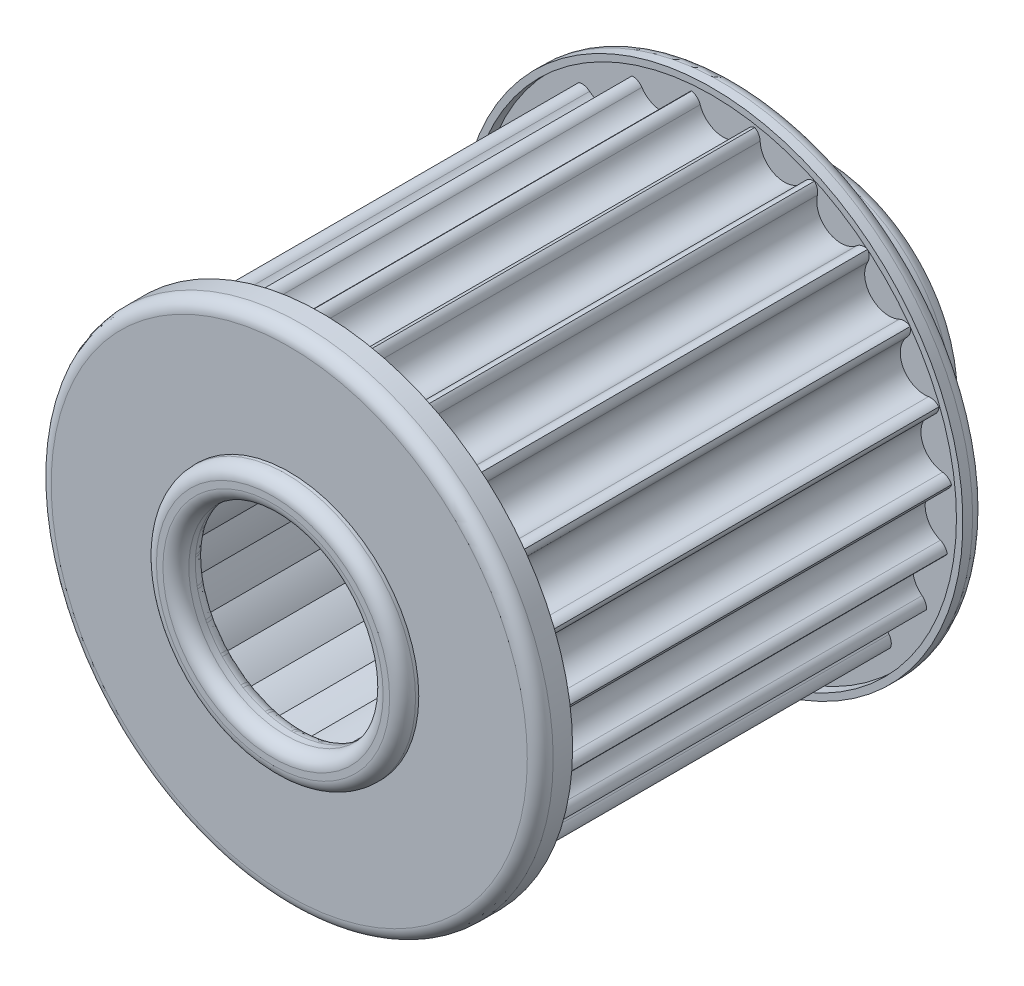
SolidWorks part; units mm, degrees
ref_plane "Front Plane" through (0, 0, 0) normal (0, 0, 1) x (1, 0, 0)
ref_plane "Top Plane" through (0, 0, 0) normal (0, 1, 0) x (1, 0, 0)
ref_plane "Right Plane" through (0, 0, 0) normal (1, 0, 0) x (0, 0, -1)
sketch "Sketch2" plane through (0, 0, 0) normal (0, 1, 0) x (1, 0, 0)
  line L0 (37.5, 21.1002) -> (37.5, 17.6002)
  line L1 (37.5, 17.6002) -> (39.5, 17.6002)
  line L2 (39.5, 17.6002) -> (39.5, 21.1002)
  line L10 (0, 52.6002) -> (0, 0.224) construction
  line L11 (43, 52.6002) -> (37.5, 52.6002)
  line L12 (75.5, 21.1002) -> (75.5, 17.6002)
  line L13 (75.5, 17.6002) -> (77.5, 17.6002)
  line L14 (77.5, 17.6002) -> (77.5, 24.6002)
  line L15 (77.5, 24.6002) -> (50, 24.6002)
  line L16 (50, 24.6002) -> (43, 31.6002)
  line L17 (43, 31.6002) -> (43, 52.6002)
  line L18 (37.5, 52.6002) -> (37.5, 21.1002)
  line L19 (39.5, 21.1002) -> (75.5, 21.1002)
  dimension "D1" = 37.5
  dimension "D2" = 2
revolve "Revolve2" add sketch "Sketch2" angle 360 about L10
sketch "Sketch3" plane through (0, 0, -21.1002) normal (0, 0, 1) x (1, 0, 0)
  circle A0 centre (0, 0) radius 72.5
  dimension "D1" = 145
extrude "Boss-Extrude1" add sketch "Sketch3" along normal blind 128
sketch "Sketch4" plane through (0, 0, 106.8998) normal (0, 0, 1) x (1, 0, 0)
  line L0 (7.5, 70) -> (10, 70)
  line L1 (-10, 70) -> (-7.5, 70)
  line L2 (-10, 70) -> (-10, 74.8348)
  line L4 (10, 70) -> (10, 74.8348)
  arc A0 (-7.5, 70) -> (7.5, 70) centre (0, 70) ccw
  circle A1 centre (0, 0) radius 75.5 construction
  arc A2 (10, 74.8348) -> (-10, 74.8348) centre (0, 0) ccw
  dimension "D1" = 15
  dimension "D2" = 70
  dimension "D3" = 10
  dimension "D4" = 10
extrude "Cut-Extrude1" cut sketch "Sketch4" against normal up to surface (128 mm away) up to face at (-72.5, 0, -21.1002)
fillet "Fillet1" radius 3.5 2 edges at (7.5, 70, 42.8998) (-7.5, 70, 42.8998)
pattern_circular "CirPattern1" count 23 over 360 about axis through (0, 0, 106.8998) along (0, 0, 1) of "Cut-Extrude1", "Fillet1"
sketch "Sketch5" plane through (0, 0, 106.8998) normal (0, 0, 1) x (1, 0, 0)
  arc A0 (-34.5026, 42.4094) -> (-21.7812, 50.1454) centre (-36.3709, 59.8094) ccw
  arc A1 (-21.7812, 50.1454) -> (-21.7812, 50.1454) centre (-21.7812, 50.1454) ccw
  arc A2 (-21.7812, 50.1454) -> (-21.7812, 50.1454) centre (-21.7812, 50.1454) ccw
  arc A3 (-21.7812, 50.1454) -> (-7.4444, 54.1624) centre (-18.8858, 67.4042) ccw
  arc A4 (-7.4444, 54.1624) -> (-7.4444, 54.1624) centre (-7.4444, 54.1624) ccw
  arc A5 (-7.4444, 54.1624) -> (-7.4444, 54.1624) centre (-7.4444, 54.1624) ccw
  arc A6 (-7.4444, 54.1624) -> (7.4444, 54.1624) centre (0, 70) ccw
  arc A7 (7.4444, 54.1624) -> (7.4444, 54.1624) centre (7.4444, 54.1624) ccw
  arc A8 (7.4444, 54.1624) -> (7.4444, 54.1624) centre (7.4444, 54.1624) ccw
  arc A9 (7.4444, 54.1624) -> (21.7812, 50.1454) centre (18.8858, 67.4042) ccw
  arc A10 (21.7812, 50.1454) -> (21.7812, 50.1454) centre (21.7812, 50.1454) ccw
  arc A11 (21.7812, 50.1454) -> (21.7812, 50.1454) centre (21.7812, 50.1454) ccw
  arc A12 (21.7812, 50.1454) -> (34.5026, 42.4094) centre (36.3709, 59.8094) ccw
  arc A13 (34.5026, 42.4094) -> (34.5026, 42.4094) centre (34.5026, 42.4094) ccw
  arc A14 (34.5026, 42.4094) -> (34.5026, 42.4094) centre (34.5026, 42.4094) ccw
  arc A15 (34.5026, 42.4094) -> (44.665, 31.528) centre (51.1585, 47.7787) ccw
  arc A16 (44.665, 31.528) -> (44.665, 31.528) centre (44.665, 31.528) ccw
  arc A17 (44.665, 31.528) -> (44.665, 31.528) centre (44.665, 31.528) ccw
  arc A18 (44.665, 31.528) -> (51.5149, 18.3084) centre (62.152, 32.2046) ccw
  arc A19 (51.5149, 18.3084) -> (51.5149, 18.3084) centre (51.5149, 18.3084) ccw
  arc A20 (51.5149, 18.3084) -> (51.5149, 18.3084) centre (51.5149, 18.3084) ccw
  arc A21 (51.5149, 18.3084) -> (54.5441, 3.7309) centre (68.5359, 14.2419) ccw
  arc A22 (54.5441, 3.7309) -> (54.5441, 3.7309) centre (54.5441, 3.7309) ccw
  arc A23 (54.5441, 3.7309) -> (54.5441, 3.7309) centre (54.5441, 3.7309) ccw
  arc A24 (54.5441, 3.7309) -> (53.5281, -11.1233) centre (69.8368, -4.777) ccw
  arc A25 (53.5281, -11.1233) -> (53.5281, -11.1233) centre (53.5281, -11.1233) ccw
  arc A26 (53.5281, -11.1233) -> (53.5281, -11.1233) centre (53.5281, -11.1233) ccw
  arc A27 (53.5281, -11.1233) -> (48.5421, -25.1525) centre (65.9583, -23.4416) ccw
  arc A28 (48.5421, -25.1525) -> (48.5421, -25.1525) centre (48.5421, -25.1525) ccw
  arc A29 (48.5421, -25.1525) -> (48.5421, -25.1525) centre (48.5421, -25.1525) ccw
  arc A30 (48.5421, -25.1525) -> (39.956, -37.3163) centre (57.1879, -40.3676) ccw
  arc A31 (39.956, -37.3163) -> (39.956, -37.3163) centre (39.956, -37.3163) ccw
  arc A32 (39.956, -37.3163) -> (39.956, -37.3163) centre (39.956, -37.3163) ccw
  arc A33 (39.956, -37.3163) -> (28.4065, -46.7125) centre (44.1762, -54.2998) ccw
  arc A34 (28.4065, -46.7125) -> (28.4065, -46.7125) centre (28.4065, -46.7125) ccw
  arc A35 (28.4065, -46.7125) -> (28.4065, -46.7125) centre (28.4065, -46.7125) ccw
  arc A36 (28.4065, -46.7125) -> (14.7502, -52.6442) centre (27.8881, -64.2048) ccw
  arc A37 (14.7502, -52.6442) -> (14.7502, -52.6442) centre (14.7502, -52.6442) ccw
  arc A38 (14.7502, -52.6442) -> (14.7502, -52.6442) centre (14.7502, -52.6442) ccw
  arc A39 (14.7502, -52.6442) -> (0, -54.6716) centre (9.5317, -69.348) ccw
  arc A40 (0, -54.6716) -> (0, -54.6716) centre (0, -54.6716) ccw
  arc A41 (0, -54.6716) -> (0, -54.6716) centre (0, -54.6716) ccw
  arc A42 (0, -54.6716) -> (-14.7502, -52.6442) centre (-9.5317, -69.348) ccw
  arc A43 (-14.7502, -52.6442) -> (-14.7502, -52.6442) centre (-14.7502, -52.6442) ccw
  arc A44 (-14.7502, -52.6442) -> (-14.7502, -52.6442) centre (-14.7502, -52.6442) ccw
  arc A45 (-14.7502, -52.6442) -> (-28.4065, -46.7125) centre (-27.8881, -64.2048) ccw
  arc A46 (-28.4065, -46.7125) -> (-28.4065, -46.7125) centre (-28.4065, -46.7125) ccw
  arc A47 (-28.4065, -46.7125) -> (-28.4065, -46.7125) centre (-28.4065, -46.7125) ccw
  arc A48 (-28.4065, -46.7125) -> (-39.956, -37.3163) centre (-44.1762, -54.2998) ccw
  arc A49 (-39.956, -37.3163) -> (-39.956, -37.3163) centre (-39.956, -37.3163) ccw
  arc A50 (-39.956, -37.3163) -> (-39.956, -37.3163) centre (-39.956, -37.3163) ccw
  arc A51 (-39.956, -37.3163) -> (-48.5421, -25.1525) centre (-57.1879, -40.3676) ccw
  arc A52 (-48.5421, -25.1525) -> (-48.5421, -25.1525) centre (-48.5421, -25.1525) ccw
  arc A53 (-48.5421, -25.1525) -> (-48.5421, -25.1525) centre (-48.5421, -25.1525) ccw
  arc A54 (-48.5421, -25.1525) -> (-53.5281, -11.1233) centre (-65.9583, -23.4416) ccw
  arc A55 (-53.5281, -11.1233) -> (-53.5281, -11.1233) centre (-53.5281, -11.1233) ccw
  arc A56 (-53.5281, -11.1233) -> (-53.5281, -11.1233) centre (-53.5281, -11.1233) ccw
  arc A57 (-53.5281, -11.1233) -> (-54.5441, 3.7309) centre (-69.8368, -4.777) ccw
  arc A58 (-54.5441, 3.7309) -> (-54.5441, 3.7309) centre (-54.5441, 3.7309) ccw
  arc A59 (-54.5441, 3.7309) -> (-54.5441, 3.7309) centre (-54.5441, 3.7309) ccw
  arc A60 (-54.5441, 3.7309) -> (-51.5149, 18.3084) centre (-68.5359, 14.2419) ccw
  arc A61 (-51.5149, 18.3084) -> (-51.5149, 18.3084) centre (-51.5149, 18.3084) ccw
  arc A62 (-51.5149, 18.3084) -> (-51.5149, 18.3084) centre (-51.5149, 18.3084) ccw
  arc A63 (-51.5149, 18.3084) -> (-44.665, 31.528) centre (-62.152, 32.2046) ccw
  arc A64 (-44.665, 31.528) -> (-44.665, 31.528) centre (-44.665, 31.528) ccw
  arc A65 (-44.665, 31.528) -> (-44.665, 31.528) centre (-44.665, 31.528) ccw
  arc A66 (-44.665, 31.528) -> (-34.5026, 42.4094) centre (-51.1585, 47.7787) ccw
  arc A67 (-34.5026, 42.4094) -> (-34.5026, 42.4094) centre (-34.5026, 42.4094) ccw
  arc A68 (-34.5026, 42.4094) -> (-34.5026, 42.4094) centre (-34.5026, 42.4094) ccw
  arc A69 (29.0724, 61.5365) -> (28.1503, 64.8084) centre (25.6665, 62.3425) ccw
  arc A70 (28.1503, 64.8084) -> (25.1296, 63.2491) centre (28.0434, 61.3101) ccw
  arc A71 (11.3908, 67.1289) -> (25.1296, 63.2491) centre (18.8858, 67.4042) ccw
  arc A72 (11.3908, 67.1289) -> (9.7597, 69.9612) centre (7.8932, 67.0005) ccw
  arc A73 (9.7597, 69.9612) -> (7.1165, 67.6324) centre (10.4375, 66.5275) ccw
  arc A74 (-7.1165, 67.6324) -> (7.1165, 67.6324) centre (0, 70) ccw
  arc A75 (-7.1165, 67.6324) -> (-9.7597, 69.9612) centre (-10.4375, 66.5275) ccw
  arc A76 (-9.7597, 69.9612) -> (-11.3908, 67.1289) centre (-7.8932, 67.0005) ccw
  arc A77 (-25.1296, 63.2491) -> (-11.3908, 67.1289) centre (-18.8858, 67.4042) ccw
  arc A78 (-25.1296, 63.2491) -> (-28.1503, 64.8084) centre (-28.0434, 61.3101) ccw
  arc A79 (-28.1503, 64.8084) -> (-29.0724, 61.5365) centre (-25.6665, 62.3425) ccw
  arc A80 (-41.2621, 54.1238) -> (-29.0724, 61.5365) centre (-36.3709, 59.8094) ccw
  arc A81 (-41.2621, 54.1238) -> (-44.5915, 54.8103) centre (-43.5447, 51.4705) ccw
  arc A82 (-44.5915, 54.8103) -> (-44.5967, 51.4109) centre (-41.5345, 53.1059) ccw
  arc A83 (-54.3344, 40.9843) -> (-44.5967, 51.4109) centre (-51.1585, 47.7787) ccw
  arc A84 (-54.3344, 40.9843) -> (-57.7256, 40.7471) centre (-55.8165, 37.8136) ccw
  arc A85 (-57.7256, 40.7471) -> (-56.8134, 37.4724) centre (-54.3221, 39.9307) ccw
  arc A86 (-63.377, 24.8053) -> (-56.8134, 37.4724) centre (-62.152, 32.2046) ccw
  arc A87 (-63.377, 24.8053) -> (-66.5784, 23.662) centre (-63.9487, 21.3523) ccw
  arc A88 (-66.5784, 23.662) -> (-64.8166, 20.7547) centre (-63.0809, 23.794) ccw
  arc A89 (-67.7192, 6.7865) -> (-64.8166, 20.7547) centre (-68.5359, 14.2419) ccw
  arc A90 (-67.7192, 6.7865) -> (-70.4934, 4.8219) centre (-67.3381, 3.3073) ccw
  arc A91 (-70.4934, 4.8219) -> (-68.0125, 2.4978) centre (-67.1612, 5.8927) ccw
  arc A92 (-67.039, -11.7356) -> (-68.0125, 2.4978) centre (-69.8368, -4.777) ccw
  arc A93 (-67.039, -11.7356) -> (-69.1802, -14.3758) centre (-65.7333, -14.9829) ccw
  arc A94 (-69.1802, -14.3758) -> (-66.1643, -15.9444) centre (-66.2605, -12.4457) ccw
  arc A95 (-61.3868, -29.3873) -> (-66.1643, -15.9444) centre (-65.9583, -23.4416) ccw
  arc A96 (-61.3868, -29.3873) -> (-62.7363, -32.5073) centre (-59.2534, -32.1619) ccw
  arc A97 (-62.7363, -32.5073) -> (-59.409, -33.2041) centre (-60.4456, -29.8611) ccw
  arc A98 (-51.1818, -44.8595) -> (-59.409, -33.2041) centre (-57.1879, -40.3676) ccw
  arc A99 (-51.1818, -44.8595) -> (-51.6395, -48.2279) centre (-48.3789, -46.9556) ccw
  arc A100 (-51.6395, -48.2279) -> (-48.2476, -48.0011) centre (-50.1477, -45.0618) ccw
  arc A101 (-37.1809, -57.0046) -> (-48.2476, -48.0011) centre (-44.1762, -54.2998) ccw
  arc A102 (-37.1809, -57.0046) -> (-36.7128, -60.3717) centre (-33.9164, -58.2669) ccw
  arc A103 (-36.7128, -60.3717) -> (-33.5079, -59.2382) centre (-36.1305, -56.9204) ccw
  arc A104 (-20.4224, -64.922) -> (-33.5079, -59.2382) centre (-27.8881, -64.2048) ccw
  arc A105 (-20.4224, -64.922) -> (-19.0633, -68.0379) centre (-16.9385, -65.2567) ccw
  arc A106 (-19.0633, -68.0379) -> (-16.2831, -66.0818) centre (-19.4338, -64.5576) ccw
  arc A107 (-2.1494, -68.0244) -> (-16.2831, -66.0818) centre (-9.5317, -69.348) ccw
  arc A108 (-2.1494, -68.0244) -> (0, -70.6581) centre (1.2957, -67.4068) ccw
  arc A109 (0, -70.6581) -> (2.1494, -68.0244) centre (-1.2957, -67.4068) ccw
  arc A110 (16.2831, -66.0818) -> (2.1494, -68.0244) centre (9.5317, -69.348) ccw
  arc A111 (16.2831, -66.0818) -> (19.0633, -68.0379) centre (19.4338, -64.5576) ccw
  arc A112 (19.0633, -68.0379) -> (20.4224, -64.922) centre (16.9385, -65.2567) ccw
  arc A113 (33.5079, -59.2382) -> (20.4224, -64.922) centre (27.8881, -64.2048) ccw
  arc A114 (33.5079, -59.2382) -> (36.7128, -60.3717) centre (36.1305, -56.9204) ccw
  arc A115 (36.7128, -60.3717) -> (37.1809, -57.0046) centre (33.9164, -58.2669) ccw
  arc A116 (48.2476, -48.0011) -> (37.1809, -57.0046) centre (44.1762, -54.2998) ccw
  arc A117 (48.2476, -48.0011) -> (51.6395, -48.2279) centre (50.1477, -45.0618) ccw
  arc A118 (51.6395, -48.2279) -> (51.1818, -44.8595) centre (48.3789, -46.9556) ccw
  arc A119 (59.409, -33.2041) -> (51.1818, -44.8595) centre (57.1879, -40.3676) ccw
  arc A120 (59.409, -33.2041) -> (62.7363, -32.5073) centre (60.4456, -29.8611) ccw
  arc A121 (62.7363, -32.5073) -> (61.3868, -29.3873) centre (59.2534, -32.1619) ccw
  arc A122 (66.1643, -15.9444) -> (61.3868, -29.3873) centre (65.9583, -23.4416) ccw
  arc A123 (66.1643, -15.9444) -> (69.1802, -14.3758) centre (66.2605, -12.4457) ccw
  arc A124 (69.1802, -14.3758) -> (67.039, -11.7356) centre (65.7333, -14.9829) ccw
  arc A125 (68.0125, 2.4978) -> (67.039, -11.7356) centre (69.8368, -4.777) ccw
  arc A126 (68.0125, 2.4978) -> (70.4934, 4.8219) centre (67.1612, 5.8927) ccw
  arc A127 (70.4934, 4.8219) -> (67.7192, 6.7865) centre (67.3381, 3.3073) ccw
  arc A128 (64.8166, 20.7547) -> (67.7192, 6.7865) centre (68.5359, 14.2419) ccw
  arc A129 (64.8166, 20.7547) -> (66.5784, 23.662) centre (63.0809, 23.794) ccw
  arc A130 (66.5784, 23.662) -> (63.377, 24.8053) centre (63.9487, 21.3523) ccw
  arc A131 (56.8134, 37.4724) -> (63.377, 24.8053) centre (62.152, 32.2046) ccw
  arc A132 (56.8134, 37.4724) -> (57.7256, 40.7471) centre (54.3221, 39.9307) ccw
  arc A133 (57.7256, 40.7471) -> (54.3344, 40.9843) centre (55.8165, 37.8136) ccw
  arc A134 (44.5967, 51.4109) -> (54.3344, 40.9843) centre (51.1585, 47.7787) ccw
  arc A135 (44.5967, 51.4109) -> (44.5915, 54.8103) centre (41.5345, 53.1059) ccw
  arc A136 (44.5915, 54.8103) -> (41.2621, 54.1238) centre (43.5447, 51.4705) ccw
  arc A137 (29.0724, 61.5365) -> (41.2621, 54.1238) centre (36.3709, 59.8094) ccw
  arc A138 (29.0724, 61.5365) -> (28.1503, 64.8084) centre (25.6665, 62.3425) ccw
  arc A139 (28.1503, 64.8084) -> (25.1296, 63.2491) centre (28.0434, 61.3101) ccw
  arc A141 (11.3908, 67.1289) -> (9.7597, 69.9612) centre (7.8932, 67.0005) ccw
  arc A142 (9.7597, 69.9612) -> (7.1165, 67.6324) centre (10.4375, 66.5275) ccw
  arc A144 (-7.1165, 67.6324) -> (-9.7597, 69.9612) centre (-10.4375, 66.5275) ccw
  arc A150 (-41.2621, 54.1238) -> (-44.5915, 54.8103) centre (-43.5447, 51.4705) ccw
  arc A151 (-44.5915, 54.8103) -> (-44.5967, 51.4109) centre (-41.5345, 53.1059) ccw
  arc A153 (-54.3344, 40.9843) -> (-57.7256, 40.7471) centre (-55.8165, 37.8136) ccw
  arc A154 (-57.7256, 40.7471) -> (-56.8134, 37.4724) centre (-54.3221, 39.9307) ccw
  arc A155 (-63.377, 24.8053) -> (-56.8134, 37.4724) centre (-62.152, 32.2046) ccw
  arc A156 (-63.377, 24.8053) -> (-66.5784, 23.662) centre (-63.9487, 21.3523) ccw
  arc A157 (-66.5784, 23.662) -> (-64.8166, 20.7547) centre (-63.0809, 23.794) ccw
  arc A162 (-67.039, -11.7356) -> (-69.1802, -14.3758) centre (-65.7333, -14.9829) ccw
  arc A163 (-69.1802, -14.3758) -> (-66.1643, -15.9444) centre (-66.2605, -12.4457) ccw
  arc A165 (-61.3868, -29.3873) -> (-62.7363, -32.5073) centre (-59.2534, -32.1619) ccw
  arc A166 (-62.7363, -32.5073) -> (-59.409, -33.2041) centre (-60.4456, -29.8611) ccw
  arc A168 (-51.1818, -44.8595) -> (-51.6395, -48.2279) centre (-48.3789, -46.9556) ccw
  arc A169 (-51.6395, -48.2279) -> (-48.2476, -48.0011) centre (-50.1477, -45.0618) ccw
  arc A171 (-37.1809, -57.0046) -> (-36.7128, -60.3717) centre (-33.9164, -58.2669) ccw
  arc A172 (-36.7128, -60.3717) -> (-33.5079, -59.2382) centre (-36.1305, -56.9204) ccw
  arc A174 (-20.4224, -64.922) -> (-19.0633, -68.0379) centre (-16.9385, -65.2567) ccw
  arc A175 (-19.0633, -68.0379) -> (-16.2831, -66.0818) centre (-19.4338, -64.5576) ccw
  arc A177 (-2.1494, -68.0244) -> (0, -70.6581) centre (1.2957, -67.4068) ccw
  arc A178 (0, -70.6581) -> (2.1494, -68.0244) centre (-1.2957, -67.4068) ccw
  arc A180 (16.2831, -66.0818) -> (19.0633, -68.0379) centre (19.4338, -64.5576) ccw
  arc A181 (19.0633, -68.0379) -> (20.4224, -64.922) centre (16.9385, -65.2567) ccw
  arc A183 (33.5079, -59.2382) -> (36.7128, -60.3717) centre (36.1305, -56.9204) ccw
  arc A184 (36.7128, -60.3717) -> (37.1809, -57.0046) centre (33.9164, -58.2669) ccw
  arc A186 (48.2476, -48.0011) -> (51.6395, -48.2279) centre (50.1477, -45.0618) ccw
  arc A187 (51.6395, -48.2279) -> (51.1818, -44.8595) centre (48.3789, -46.9556) ccw
  arc A188 (59.409, -33.2041) -> (51.1818, -44.8595) centre (57.1879, -40.3676) ccw
  arc A189 (59.409, -33.2041) -> (62.7363, -32.5073) centre (60.4456, -29.8611) ccw
  arc A190 (62.7363, -32.5073) -> (61.3868, -29.3873) centre (59.2534, -32.1619) ccw
  arc A192 (66.1643, -15.9444) -> (69.1802, -14.3758) centre (66.2605, -12.4457) ccw
  arc A193 (69.1802, -14.3758) -> (67.039, -11.7356) centre (65.7333, -14.9829) ccw
  arc A197 (64.8166, 20.7547) -> (67.7192, 6.7865) centre (68.5359, 14.2419) ccw
  arc A199 (66.5784, 23.662) -> (63.377, 24.8053) centre (63.9487, 21.3523) ccw
  arc A201 (56.8134, 37.4724) -> (57.7256, 40.7471) centre (54.3221, 39.9307) ccw
  arc A202 (57.7256, 40.7471) -> (54.3344, 40.9843) centre (55.8165, 37.8136) ccw
  arc A204 (44.5967, 51.4109) -> (44.5915, 54.8103) centre (41.5345, 53.1059) ccw
  arc A205 (44.5915, 54.8103) -> (41.2621, 54.1238) centre (43.5447, 51.4705) ccw
  arc A207 (29.0724, 61.5365) -> (41.2621, 54.1238) centre (36.3709, 59.8094) ccw construction
  arc A208 (-7.1165, 67.6324) -> (7.1165, 67.6324) centre (0, 70) ccw construction
  arc A209 (-9.7597, 69.9612) -> (-11.3908, 67.1289) centre (-7.8932, 67.0005) ccw construction
  arc A210 (-25.1296, 63.2491) -> (-28.1503, 64.8084) centre (-28.0434, 61.3101) ccw construction
  arc A211 (-28.1503, 64.8084) -> (-29.0724, 61.5365) centre (-25.6665, 62.3425) ccw construction
  arc A212 (-41.2621, 54.1238) -> (-29.0724, 61.5365) centre (-36.3709, 59.8094) ccw construction
  arc A213 (-25.1296, 63.2491) -> (-11.3908, 67.1289) centre (-18.8858, 67.4042) ccw construction
  arc A214 (-54.3344, 40.9843) -> (-44.5967, 51.4109) centre (-51.1585, 47.7787) ccw construction
  arc A215 (-67.7192, 6.7865) -> (-64.8166, 20.7547) centre (-68.5359, 14.2419) ccw construction
  arc A216 (-67.7192, 6.7865) -> (-70.4934, 4.8219) centre (-67.3381, 3.3073) ccw construction
  arc A217 (-70.4934, 4.8219) -> (-68.0125, 2.4978) centre (-67.1612, 5.8927) ccw construction
  arc A218 (-67.039, -11.7356) -> (-68.0125, 2.4978) centre (-69.8368, -4.777) ccw construction
  arc A219 (-61.3868, -29.3873) -> (-66.1643, -15.9444) centre (-65.9583, -23.4416) ccw construction
  arc A220 (-51.1818, -44.8595) -> (-59.409, -33.2041) centre (-57.1879, -40.3676) ccw construction
  arc A221 (-37.1809, -57.0046) -> (-48.2476, -48.0011) centre (-44.1762, -54.2998) ccw construction
  arc A222 (-20.4224, -64.922) -> (-33.5079, -59.2382) centre (-27.8881, -64.2048) ccw construction
  arc A223 (-2.1494, -68.0244) -> (-16.2831, -66.0818) centre (-9.5317, -69.348) ccw construction
  arc A224 (16.2831, -66.0818) -> (2.1494, -68.0244) centre (9.5317, -69.348) ccw construction
  arc A225 (33.5079, -59.2382) -> (20.4224, -64.922) centre (27.8881, -64.2048) ccw construction
  arc A226 (48.2476, -48.0011) -> (37.1809, -57.0046) centre (44.1762, -54.2998) ccw construction
  arc A227 (66.1643, -15.9444) -> (61.3868, -29.3873) centre (65.9583, -23.4416) ccw construction
  arc A228 (68.0125, 2.4978) -> (67.039, -11.7356) centre (69.8368, -4.777) ccw construction
  arc A229 (68.0125, 2.4978) -> (70.4934, 4.8219) centre (67.1612, 5.8927) ccw construction
  arc A230 (70.4934, 4.8219) -> (67.7192, 6.7865) centre (67.3381, 3.3073) ccw construction
  arc A231 (64.8166, 20.7547) -> (66.5784, 23.662) centre (63.0809, 23.794) ccw construction
  arc A232 (56.8134, 37.4724) -> (63.377, 24.8053) centre (62.152, 32.2046) ccw construction
  arc A233 (44.5967, 51.4109) -> (54.3344, 40.9843) centre (51.1585, 47.7787) ccw construction
  arc A234 (11.3908, 67.1289) -> (25.1296, 63.2491) centre (18.8858, 67.4042) ccw construction
  dimension "D1" = 0
  dimension "D2" = 10
extrude "Cut-Extrude2" cut sketch "Sketch5" against normal blind 128 contours A66 A63 A60 A57 A54 A51 A48 A45 A42 A39 A36 A33 A30 A27 A24 A21 A18 A15 A12 A9 A6 A3 A0 region at (0, 0, 106.8998)
ref_plane "Plane1" through (0, 0, 59.3998) normal (0, 0, -1) x (-1, 0, 0)
sketch "Sketch6" plane through (0, 0, 59.3998) normal (0, 0, -1) x (-1, 0, 0)
  arc A23 (34.5026, 42.4094) -> (44.665, 31.528) centre (51.1585, 47.7787) ccw
  arc A24 (44.665, 31.528) -> (51.5149, 18.3084) centre (62.152, 32.2046) ccw
  arc A25 (51.5149, 18.3084) -> (54.5441, 3.7309) centre (68.5359, 14.2419) ccw
  arc A26 (54.5441, 3.7309) -> (53.5281, -11.1233) centre (69.8368, -4.777) ccw
  arc A27 (53.5281, -11.1233) -> (48.5421, -25.1525) centre (65.9583, -23.4416) ccw
  arc A28 (48.5421, -25.1525) -> (39.956, -37.3163) centre (57.1879, -40.3676) ccw
  arc A29 (39.956, -37.3163) -> (28.4065, -46.7125) centre (44.1762, -54.2998) ccw
  arc A30 (28.4065, -46.7125) -> (14.7502, -52.6442) centre (27.8881, -64.2048) ccw
  arc A31 (14.7502, -52.6442) -> (0, -54.6716) centre (9.5317, -69.348) ccw
  arc A32 (0, -54.6716) -> (-14.7502, -52.6442) centre (-9.5317, -69.348) ccw
  arc A33 (-14.7502, -52.6442) -> (-28.4065, -46.7125) centre (-27.8881, -64.2048) ccw
  arc A34 (-28.4065, -46.7125) -> (-39.956, -37.3163) centre (-44.1762, -54.2998) ccw
  arc A35 (-39.956, -37.3163) -> (-48.5421, -25.1525) centre (-57.1879, -40.3676) ccw
  arc A36 (-48.5421, -25.1525) -> (-53.5281, -11.1233) centre (-65.9583, -23.4416) ccw
  arc A37 (-53.5281, -11.1233) -> (-54.5441, 3.7309) centre (-69.8368, -4.777) ccw
  arc A38 (-54.5441, 3.7309) -> (-51.5149, 18.3084) centre (-68.5359, 14.2419) ccw
  arc A39 (-51.5149, 18.3084) -> (-44.665, 31.528) centre (-62.152, 32.2046) ccw
  arc A40 (-44.665, 31.528) -> (-34.5026, 42.4094) centre (-51.1585, 47.7787) ccw
  arc A41 (-34.5026, 42.4094) -> (-21.7812, 50.1454) centre (-36.3709, 59.8094) ccw
  arc A42 (-21.7812, 50.1454) -> (-7.4444, 54.1624) centre (-18.8858, 67.4042) ccw
  arc A43 (-7.4444, 54.1624) -> (7.4444, 54.1624) centre (0, 70) ccw
  arc A44 (7.4444, 54.1624) -> (21.7812, 50.1454) centre (18.8858, 67.4042) ccw
  arc A45 (21.7812, 50.1454) -> (34.5026, 42.4094) centre (36.3709, 59.8094) ccw
  arc A46 (34.5026, 42.4094) -> (44.665, 31.528) centre (51.1585, 47.7787) ccw
  arc A47 (44.665, 31.528) -> (51.5149, 18.3084) centre (62.152, 32.2046) ccw
  arc A48 (51.5149, 18.3084) -> (54.5441, 3.7309) centre (68.5359, 14.2419) ccw
  arc A49 (54.5441, 3.7309) -> (53.5281, -11.1233) centre (69.8368, -4.777) ccw
  arc A50 (53.5281, -11.1233) -> (48.5421, -25.1525) centre (65.9583, -23.4416) ccw
  arc A51 (48.5421, -25.1525) -> (39.956, -37.3163) centre (57.1879, -40.3676) ccw
  arc A52 (39.956, -37.3163) -> (28.4065, -46.7125) centre (44.1762, -54.2998) ccw
  arc A53 (28.4065, -46.7125) -> (14.7502, -52.6442) centre (27.8881, -64.2048) ccw
  arc A54 (14.7502, -52.6442) -> (0, -54.6716) centre (9.5317, -69.348) ccw
  arc A55 (0, -54.6716) -> (-14.7502, -52.6442) centre (-9.5317, -69.348) ccw
  arc A56 (-14.7502, -52.6442) -> (-28.4065, -46.7125) centre (-27.8881, -64.2048) ccw
  arc A57 (-28.4065, -46.7125) -> (-39.956, -37.3163) centre (-44.1762, -54.2998) ccw
  arc A58 (-39.956, -37.3163) -> (-48.5421, -25.1525) centre (-57.1879, -40.3676) ccw
  arc A59 (-48.5421, -25.1525) -> (-53.5281, -11.1233) centre (-65.9583, -23.4416) ccw
  arc A60 (-53.5281, -11.1233) -> (-54.5441, 3.7309) centre (-69.8368, -4.777) ccw
  arc A61 (-54.5441, 3.7309) -> (-51.5149, 18.3084) centre (-68.5359, 14.2419) ccw
  arc A62 (-51.5149, 18.3084) -> (-44.665, 31.528) centre (-62.152, 32.2046) ccw
  arc A63 (-44.665, 31.528) -> (-34.5026, 42.4094) centre (-51.1585, 47.7787) ccw
  arc A64 (-34.5026, 42.4094) -> (-21.7812, 50.1454) centre (-36.3709, 59.8094) ccw
  arc A65 (-21.7812, 50.1454) -> (-7.4444, 54.1624) centre (-18.8858, 67.4042) ccw
  arc A66 (-7.4444, 54.1624) -> (7.4444, 54.1624) centre (0, 70) ccw
  arc A67 (7.4444, 54.1624) -> (21.7812, 50.1454) centre (18.8858, 67.4042) ccw
  arc A68 (21.7812, 50.1454) -> (34.5026, 42.4094) centre (36.3709, 59.8094) ccw
  dimension "D1" = 0
extrude "Boss-Extrude2" add sketch "Sketch6" along normal blind 4
sketch "Sketch7" plane through (0, 0, 106.8998) normal (0, 0, 1) x (1, 0, 0)
  circle A0 centre (0, 0) radius 77.5 construction
  circle A1 centre (0, 0) radius 77.5
extrude "Boss-Extrude3" add sketch "Sketch7" along normal blind 10 from offset 4 offset against normal yes
sketch "Sketch8" plane through (0, 0, 112.8998) normal (0, 0, 1) x (1, 0, 0)
  circle A0 centre (0, 0) radius 40
  dimension "D1" = 80
extrude "Cut-Extrude3" cut sketch "Sketch8" against normal blind 27
sketch "Sketch9" plane through (0, 0, 59.3998) normal (0, 0, 1) x (1, 0, 0)
  arc A0 (-15.2497, 35.1083) -> (-5.2121, 37.9207) centre (-18.8858, 67.4042) ccw
  arc A1 (-5.2121, 37.9207) -> (5.2121, 37.9207) centre (0, 70) ccw
  arc A2 (5.2121, 37.9207) -> (15.2497, 35.1083) centre (18.8858, 67.4042) ccw
  arc A3 (15.2497, 35.1083) -> (24.1563, 29.692) centre (36.3709, 59.8094) ccw
  arc A4 (24.1563, 29.692) -> (31.2713, 22.0737) centre (51.1585, 47.7787) ccw
  arc A5 (31.2713, 22.0737) -> (36.0671, 12.8182) centre (62.152, 32.2046) ccw
  arc A6 (36.0671, 12.8182) -> (38.1879, 2.6121) centre (68.5359, 14.2419) ccw
  arc A7 (38.1879, 2.6121) -> (37.4766, -7.7877) centre (69.8368, -4.777) ccw
  arc A8 (37.4766, -7.7877) -> (33.9857, -17.61) centre (65.9583, -23.4416) ccw
  arc A9 (33.9857, -17.61) -> (27.9743, -26.1262) centre (57.1879, -40.3676) ccw
  arc A10 (27.9743, -26.1262) -> (19.8882, -32.7048) centre (44.1762, -54.2998) ccw
  arc A11 (19.8882, -32.7048) -> (10.3271, -36.8578) centre (27.8881, -64.2048) ccw
  arc A12 (10.3271, -36.8578) -> (0, -38.2772) centre (9.5317, -69.348) ccw
  arc A13 (0, -38.2772) -> (-10.3271, -36.8578) centre (-9.5317, -69.348) ccw
  arc A14 (-10.3271, -36.8578) -> (-19.8882, -32.7048) centre (-27.8881, -64.2048) ccw
  arc A15 (-19.8882, -32.7048) -> (-27.9743, -26.1262) centre (-44.1762, -54.2998) ccw
  arc A16 (-27.9743, -26.1262) -> (-33.9857, -17.61) centre (-57.1879, -40.3676) ccw
  arc A17 (-33.9857, -17.61) -> (-37.4766, -7.7877) centre (-65.9583, -23.4416) ccw
  arc A18 (-37.4766, -7.7877) -> (-38.1879, 2.6121) centre (-69.8368, -4.777) ccw
  arc A19 (-38.1879, 2.6121) -> (-36.0671, 12.8182) centre (-68.5359, 14.2419) ccw
  arc A20 (-36.0671, 12.8182) -> (-31.2713, 22.0737) centre (-62.152, 32.2046) ccw
  arc A21 (-31.2713, 22.0737) -> (-24.1563, 29.692) centre (-51.1585, 47.7787) ccw
  arc A22 (-24.1563, 29.692) -> (-15.2497, 35.1083) centre (-36.3709, 59.8094) ccw
  arc A23 (-34.5026, 42.4094) -> (-21.7812, 50.1454) centre (-36.3709, 59.8094) ccw
  arc A24 (-44.665, 31.528) -> (-34.5026, 42.4094) centre (-51.1585, 47.7787) ccw
  arc A25 (-51.5149, 18.3084) -> (-44.665, 31.528) centre (-62.152, 32.2046) ccw
  arc A26 (-54.5441, 3.7309) -> (-51.5149, 18.3084) centre (-68.5359, 14.2419) ccw
  arc A27 (-53.5281, -11.1233) -> (-54.5441, 3.7309) centre (-69.8368, -4.777) ccw
  arc A28 (-48.5421, -25.1525) -> (-53.5281, -11.1233) centre (-65.9583, -23.4416) ccw
  arc A29 (-39.956, -37.3163) -> (-48.5421, -25.1525) centre (-57.1879, -40.3676) ccw
  arc A30 (-28.4065, -46.7125) -> (-39.956, -37.3163) centre (-44.1762, -54.2998) ccw
  arc A31 (-14.7502, -52.6442) -> (-28.4065, -46.7125) centre (-27.8881, -64.2048) ccw
  arc A32 (0, -54.6716) -> (-14.7502, -52.6442) centre (-9.5317, -69.348) ccw
  arc A33 (14.7502, -52.6442) -> (0, -54.6716) centre (9.5317, -69.348) ccw
  arc A34 (28.4065, -46.7125) -> (14.7502, -52.6442) centre (27.8881, -64.2048) ccw
  arc A35 (39.956, -37.3163) -> (28.4065, -46.7125) centre (44.1762, -54.2998) ccw
  arc A36 (48.5421, -25.1525) -> (39.956, -37.3163) centre (57.1879, -40.3676) ccw
  arc A37 (53.5281, -11.1233) -> (48.5421, -25.1525) centre (65.9583, -23.4416) ccw
  arc A38 (54.5441, 3.7309) -> (53.5281, -11.1233) centre (69.8368, -4.777) ccw
  arc A39 (51.5149, 18.3084) -> (54.5441, 3.7309) centre (68.5359, 14.2419) ccw
  arc A40 (44.665, 31.528) -> (51.5149, 18.3084) centre (62.152, 32.2046) ccw
  arc A41 (34.5026, 42.4094) -> (44.665, 31.528) centre (51.1585, 47.7787) ccw
  arc A42 (21.7812, 50.1454) -> (34.5026, 42.4094) centre (36.3709, 59.8094) ccw
  arc A43 (7.4444, 54.1624) -> (21.7812, 50.1454) centre (18.8858, 67.4042) ccw
  arc A44 (-7.4444, 54.1624) -> (7.4444, 54.1624) centre (0, 70) ccw
  arc A45 (-21.7812, 50.1454) -> (-7.4444, 54.1624) centre (-18.8858, 67.4042) ccw
  arc A54 (-14.7502, -52.6442) -> (-28.4065, -46.7125) centre (-27.8881, -64.2048) ccw
  arc A57 (28.4065, -46.7125) -> (14.7502, -52.6442) centre (27.8881, -64.2048) ccw
  arc A58 (39.956, -37.3163) -> (28.4065, -46.7125) centre (44.1762, -54.2998) ccw
  arc A59 (48.5421, -25.1525) -> (39.956, -37.3163) centre (57.1879, -40.3676) ccw
  arc A61 (54.5441, 3.7309) -> (53.5281, -11.1233) centre (69.8368, -4.777) ccw
  arc A62 (51.5149, 18.3084) -> (54.5441, 3.7309) centre (68.5359, 14.2419) ccw
  arc A63 (44.665, 31.528) -> (51.5149, 18.3084) centre (62.152, 32.2046) ccw
  arc A64 (34.5026, 42.4094) -> (44.665, 31.528) centre (51.1585, 47.7787) ccw
  arc A65 (21.7812, 50.1454) -> (34.5026, 42.4094) centre (36.3709, 59.8094) ccw
  arc A66 (7.4444, 54.1624) -> (21.7812, 50.1454) centre (18.8858, 67.4042) ccw
  arc A67 (-7.4444, 54.1624) -> (7.4444, 54.1624) centre (0, 70) ccw
  arc A68 (-21.7812, 50.1454) -> (-7.4444, 54.1624) centre (-18.8858, 67.4042) ccw
  arc A69 (-21.5293, 26.463) -> (-13.5913, 31.2902) centre (-36.3709, 59.8094) ccw
  arc A70 (-13.5913, 31.2902) -> (-4.6453, 33.7968) centre (-18.8858, 67.4042) ccw
  arc A71 (-4.6453, 33.7968) -> (4.6453, 33.7968) centre (0, 70) ccw
  arc A72 (4.6453, 33.7968) -> (13.5913, 31.2902) centre (18.8858, 67.4042) ccw
  arc A73 (13.5913, 31.2902) -> (21.5293, 26.463) centre (36.3709, 59.8094) ccw
  arc A74 (21.5293, 26.463) -> (27.8706, 19.6732) centre (51.1585, 47.7787) ccw
  arc A75 (27.8706, 19.6732) -> (32.1448, 11.4243) centre (62.152, 32.2046) ccw
  arc A76 (32.1448, 11.4243) -> (34.035, 2.3281) centre (68.5359, 14.2419) ccw
  arc A77 (34.035, 2.3281) -> (33.401, -6.9408) centre (69.8368, -4.777) ccw
  arc A78 (33.401, -6.9408) -> (30.2898, -15.6949) centre (65.9583, -23.4416) ccw
  arc A79 (30.2898, -15.6949) -> (24.9321, -23.285) centre (57.1879, -40.3676) ccw
  arc A80 (24.9321, -23.285) -> (17.7254, -29.1481) centre (44.1762, -54.2998) ccw
  arc A81 (17.7254, -29.1481) -> (9.204, -32.8495) centre (27.8881, -64.2048) ccw
  arc A82 (9.204, -32.8495) -> (0, -34.1145) centre (9.5317, -69.348) ccw
  arc A83 (0, -34.1145) -> (-9.204, -32.8495) centre (-9.5317, -69.348) ccw
  arc A84 (-9.204, -32.8495) -> (-17.7254, -29.1481) centre (-27.8881, -64.2048) ccw
  arc A85 (-17.7254, -29.1481) -> (-24.9321, -23.285) centre (-44.1762, -54.2998) ccw
  arc A86 (-24.9321, -23.285) -> (-30.2898, -15.6949) centre (-57.1879, -40.3676) ccw
  arc A87 (-30.2898, -15.6949) -> (-33.401, -6.9408) centre (-65.9583, -23.4416) ccw
  arc A88 (-33.401, -6.9408) -> (-34.035, 2.3281) centre (-69.8368, -4.777) ccw
  arc A89 (-34.035, 2.3281) -> (-32.1448, 11.4243) centre (-68.5359, 14.2419) ccw
  arc A90 (-32.1448, 11.4243) -> (-27.8706, 19.6732) centre (-62.152, 32.2046) ccw
  arc A91 (-27.8706, 19.6732) -> (-21.5293, 26.463) centre (-51.1585, 47.7787) ccw
  arc A92 (-34.5026, 42.4094) -> (-21.7812, 50.1454) centre (-36.3709, 59.8094) ccw construction
  arc A93 (-44.665, 31.528) -> (-34.5026, 42.4094) centre (-51.1585, 47.7787) ccw construction
  arc A94 (-51.5149, 18.3084) -> (-44.665, 31.528) centre (-62.152, 32.2046) ccw construction
  arc A95 (-48.5421, -25.1525) -> (-53.5281, -11.1233) centre (-65.9583, -23.4416) ccw construction
  arc A96 (-39.956, -37.3163) -> (-48.5421, -25.1525) centre (-57.1879, -40.3676) ccw construction
  arc A97 (-28.4065, -46.7125) -> (-39.956, -37.3163) centre (-44.1762, -54.2998) ccw construction
  arc A98 (0, -54.6716) -> (-14.7502, -52.6442) centre (-9.5317, -69.348) ccw construction
  arc A99 (14.7502, -52.6442) -> (0, -54.6716) centre (9.5317, -69.348) ccw construction
  arc A100 (53.5281, -11.1233) -> (48.5421, -25.1525) centre (65.9583, -23.4416) ccw construction
  arc A101 (-54.5441, 3.7309) -> (-51.5149, 18.3084) centre (-68.5359, 14.2419) ccw construction
  arc A102 (-53.5281, -11.1233) -> (-54.5441, 3.7309) centre (-69.8368, -4.777) ccw construction
  dimension "D1" = 0
  dimension "D2" = 15
  dimension "D3" = 4
extrude "Boss-Extrude4" add sketch "Sketch9" along normal up to surface (53.5 mm away) contours A19 A20 A21 A22 A0 A1 A2 A3 A4 A5 A6 A7 A8 A9 A10 A11 A12 A13 A14 A15 A16 A17 A18 | A89 A90 A91 A69 A70 A71 A72 A73 A74 A75 A76 A77 A78 A79 A80 A81 A82 A83 A84 A85 A86 A87 A88 up to face at (40, 0, 112.8998)
sketch "Sketch10" plane through (0, 0, 112.8998) normal (0, 0, 1) x (1, 0, 0)
  circle A0 centre (0, 0) radius 40 construction
  circle A1 centre (0, 0) radius 40
  circle A2 centre (0, 0) radius 30
  dimension "D1" = 10
extrude "Boss-Extrude6" add sketch "Sketch10" along normal blind 10 from offset 5 offset against normal yes
fillet "Fillet2" radius 4 6 edges at (-43, 0, -52.6002) (-77.5, 0, -24.6002) (30, 0, 107.8998) (77.5, 0, 112.8998) (30, 0, 117.8998) (40, 0, 117.8998)
